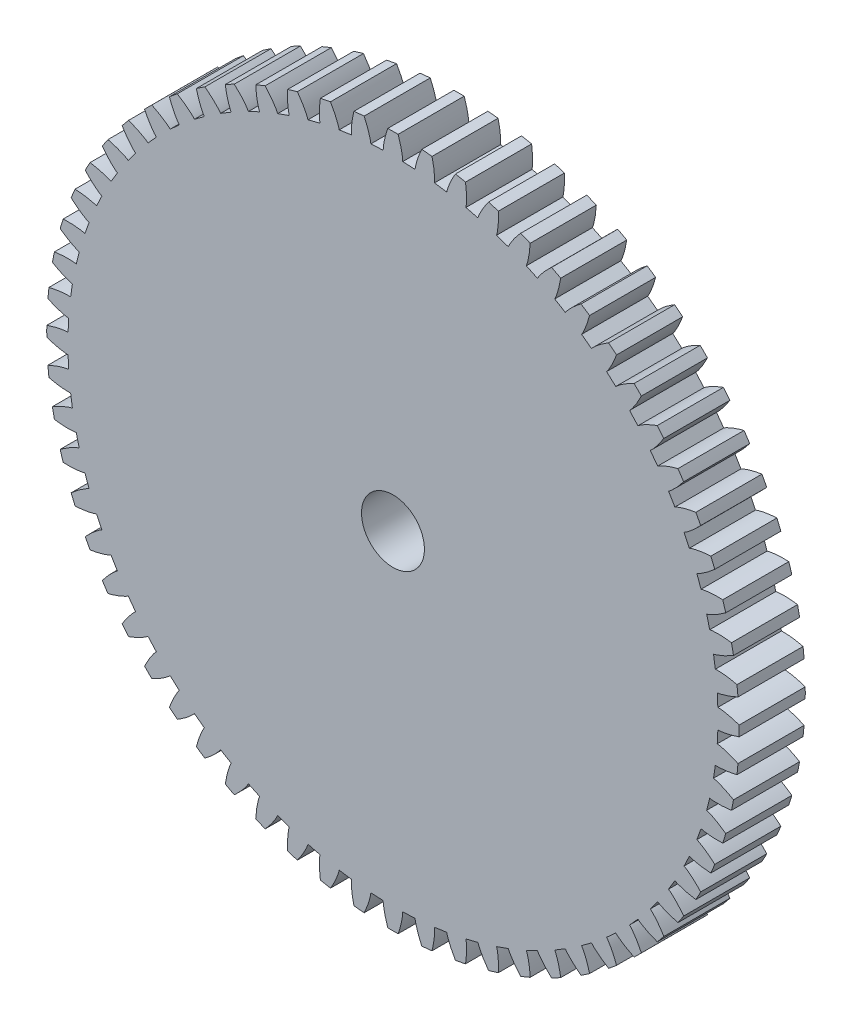
SolidWorks part; units mm, degrees
material "Plain Carbon Steel"
ref_plane "Front Plane" through (0, 0, 0) normal (0, 0, 1) x (1, 0, 0)
ref_plane "Top Plane" through (0, 0, 0) normal (0, 1, 0) x (1, 0, 0)
ref_plane "Right Plane" through (0, 0, 0) normal (1, 0, 0) x (0, 0, -1)
sketch "Sketch1" plane through (0, 0, 0) normal (0, 0, 1) x (1, 0, 0)
  circle A0 centre (0, 0) radius 52.3875
  dimension "D1" = 104.775
extrude "Boss-Extrude1" add sketch "Sketch1" along normal blind 10
sketch "Sketch2" plane through (0, 0, 0) normal (0, 0, 1) x (1, 0, 0)
  spline S0 degree 4 poles (49.1596, 1.4796) (49.1645, 1.4797) (49.1783, 1.4799) (49.2042, 1.4798) (49.2467, 1.4789) (49.3008, 1.4769) (49.3708, 1.4732) (49.4534, 1.4673) (49.5443, 1.4594) (49.6433, 1.4491) (49.7422, 1.4374) (49.841, 1.4244) (49.9396, 1.4103) (50.0592, 1.3917) (50.2028, 1.3674) (50.371, 1.3361) (50.5622, 1.2971) (50.7575, 1.2536) (50.9501, 1.2078) (51.1452, 1.158) (51.3344, 1.1072) (51.5315, 1.0509) (51.7136, 0.9971) (51.9184, 0.9327) (52.0839, 0.8796) (52.3029, 0.8051) (52.4325, 0.7599) (52.5844, 0.7054) (52.652, 0.6804) (52.6936, 0.6651) knots 0 0 0 0 0 0.005377 0.015084 0.028532 0.04661 0.064855 0.092111 0.119476 0.146842 0.174209 0.201575 0.228941 0.256307 0.307035 0.361767 0.4165 0.471232 0.525964 0.580697 0.635429 0.690161 0.744894 0.799626 0.854358 0.909091 0.954545 1 1 1 1 1 construction
  spline S1 degree 4 poles (49.1596, 1.4796) (49.1645, 1.4797) (49.1783, 1.4799) (49.2042, 1.4798) (49.2467, 1.4789) (49.3008, 1.4769) (49.3708, 1.4732) (49.4534, 1.4673) (49.5443, 1.4594) (49.6433, 1.4491) (49.7422, 1.4374) (49.841, 1.4244) (49.9396, 1.4103) (50.0592, 1.3917) (50.2028, 1.3674) (50.371, 1.3361) (50.5622, 1.2971) (50.7575, 1.2536) (50.9501, 1.2078) (51.1452, 1.158) (51.3344, 1.1072) (51.5315, 1.0509) (51.7136, 0.9971) (51.9184, 0.9327) (52.0839, 0.8796) (52.2554, 0.8213) (52.339, 0.7924) (52.3817, 0.7774) knots 0 0 0 0 0 0.005377 0.015084 0.028532 0.04661 0.064855 0.092111 0.119476 0.146842 0.174209 0.201575 0.228941 0.256307 0.307035 0.361767 0.4165 0.471232 0.525964 0.580697 0.635429 0.690161 0.744894 0.799626 0.854358 0.909091 0.909091 0.909091 0.909091 0.909091
  spline S2 degree 4 poles (49.0679, 3.346) (49.0728, 3.3464) (49.0865, 3.3476) (49.1123, 3.3502) (49.1545, 3.3552) (49.2081, 3.3625) (49.2774, 3.3731) (49.3591, 3.387) (49.4487, 3.4038) (49.5463, 3.4238) (49.6436, 3.4451) (49.7407, 3.4677) (49.8374, 3.4915) (49.9546, 3.5217) (50.0951, 3.5599) (50.2594, 3.6076) (50.4458, 3.6651) (50.6359, 3.7275) (50.8232, 3.792) (51.0125, 3.8607) (51.1957, 3.9297) (51.3863, 4.0051) (51.5624, 4.0765) (51.7599, 4.1607) (51.9193, 4.2298) (52.13, 4.3253) (52.2545, 4.3831) (52.4003, 4.4522) (52.4652, 4.4836) (52.5051, 4.503) knots 0 0 0 0 0 0.005377 0.015084 0.028532 0.04661 0.064855 0.092111 0.119476 0.146842 0.174209 0.201575 0.228941 0.256307 0.307035 0.361767 0.4165 0.471232 0.525964 0.580697 0.635429 0.690161 0.744894 0.799626 0.854358 0.909091 0.954545 1 1 1 1 1 construction
  spline S3 degree 4 poles (49.0679, 3.346) (49.0728, 3.3464) (49.0865, 3.3476) (49.1123, 3.3502) (49.1545, 3.3552) (49.2081, 3.3625) (49.2774, 3.3731) (49.3591, 3.387) (49.4487, 3.4038) (49.5463, 3.4238) (49.6436, 3.4451) (49.7407, 3.4677) (49.8374, 3.4915) (49.9546, 3.5217) (50.0951, 3.5599) (50.2594, 3.6076) (50.4458, 3.6651) (50.6359, 3.7275) (50.8232, 3.792) (51.0125, 3.8607) (51.1957, 3.9297) (51.3863, 4.0051) (51.5624, 4.0765) (51.7599, 4.1607) (51.9193, 4.2298) (52.0843, 4.3046) (52.1646, 4.3415) (52.2057, 4.3606) knots 0 0 0 0 0 0.005377 0.015084 0.028532 0.04661 0.064855 0.092111 0.119476 0.146842 0.174209 0.201575 0.228941 0.256307 0.307035 0.361767 0.4165 0.471232 0.525964 0.580697 0.635429 0.690161 0.744894 0.799626 0.854358 0.909091 0.909091 0.909091 0.909091 0.909091
  spline S4 degree 1 poles (49.0679, 3.346) (49.1596, 1.4796) knots 0 0 1 1 construction
  spline S5 degree 1 poles (49.0679, 3.346) (49.1596, 1.4796) knots 0 0 1 1
  spline S6 degree 1 poles (52.3817, 0.7774) (59.9934, 0.8904) knots 0 0 1 1 construction
  spline S7 degree 1 poles (52.3817, 0.7774) (59.9934, 0.8904) knots 0 0 1 1
  spline S8 degree 4 poles (59.9981, 0.4767) (59.9979, 0.5063) (59.9973, 0.5633) (59.9967, 0.6404) (59.9941, 0.8495) (59.9927, 0.941) (59.9881, 1.2106) (59.9845, 1.3636) (59.9793, 1.5848) (59.9741, 1.765) (59.9679, 1.9699) (59.9612, 2.1599) (59.9538, 2.3588) (59.9458, 2.5524) (59.9372, 2.7489) (59.9278, 2.9441) (59.918, 3.1392) (59.9073, 3.3356) (59.8963, 3.5291) (59.8842, 3.7277) (59.8722, 3.9174) (59.8583, 4.122) (59.8458, 4.3018) (59.8293, 4.5225) (59.8179, 4.6751) (59.7961, 4.9439) (59.7884, 5.0351) (59.7706, 5.2434) (59.7637, 5.3202) (59.7586, 5.377) (59.7559, 5.4064) knots 0 0 0 0 0 0.020959 0.041918 0.083333 0.123016 0.162698 0.202381 0.242063 0.281746 0.321429 0.361111 0.400794 0.440476 0.480159 0.519841 0.559524 0.599206 0.638889 0.678571 0.718254 0.757937 0.797619 0.837302 0.876984 0.916667 0.958082 0.979041 1 1 1 1 1 construction
  spline S9 degree 4 poles (59.9934, 0.8904) (59.9928, 0.9312) (59.9915, 1.0106) (59.9881, 1.2106) (59.9845, 1.3636) (59.9793, 1.5848) (59.9741, 1.765) (59.9679, 1.9699) (59.9612, 2.1599) (59.9538, 2.3588) (59.9458, 2.5524) (59.9372, 2.7489) (59.9278, 2.9441) (59.918, 3.1392) (59.9073, 3.3356) (59.8963, 3.5291) (59.8842, 3.7277) (59.8722, 3.9174) (59.8583, 4.122) (59.8458, 4.3018) (59.8293, 4.5225) (59.8179, 4.6751) (59.8017, 4.8745) (59.7952, 4.9536) (59.7918, 4.9943) knots 0.083333 0.083333 0.083333 0.083333 0.083333 0.123016 0.162698 0.202381 0.242063 0.281746 0.321429 0.361111 0.400794 0.440476 0.480159 0.519841 0.559524 0.599206 0.638889 0.678571 0.718254 0.757937 0.797619 0.837302 0.876984 0.916667 0.916667 0.916667 0.916667 0.916667
  spline S10 degree 1 poles (59.7918, 4.9943) (52.2057, 4.3606) knots 0 0 1 1 construction
  spline S11 degree 1 poles (59.7918, 4.9943) (52.2057, 4.3606) knots 0 0 1 1
extrude "Cut-Extrude2" cut sketch "Sketch2" against normal blind 11 and the other way blind 11
ref_axis "Axis1" through (0, 0, -0.5) along (0, 0, 1)
pattern_circular "CirPattern1" count 64 over 360 about axis through (0, 0, -0.5) along (0, 0, 1) of "Cut-Extrude2"
sketch "Sketch3" plane through (0, 0, 0) normal (0, 0, 1) x (1, 0, 0)
  circle A0 centre (0, 0) radius 4.7625
  dimension "D1" = 9.525
extrude "Cut-Extrude4" cut sketch "Sketch3" against normal blind 12 and the other way blind 12
ref_axis "Axis2" through (0, 0, -0.5) along (0, 0, 1)
